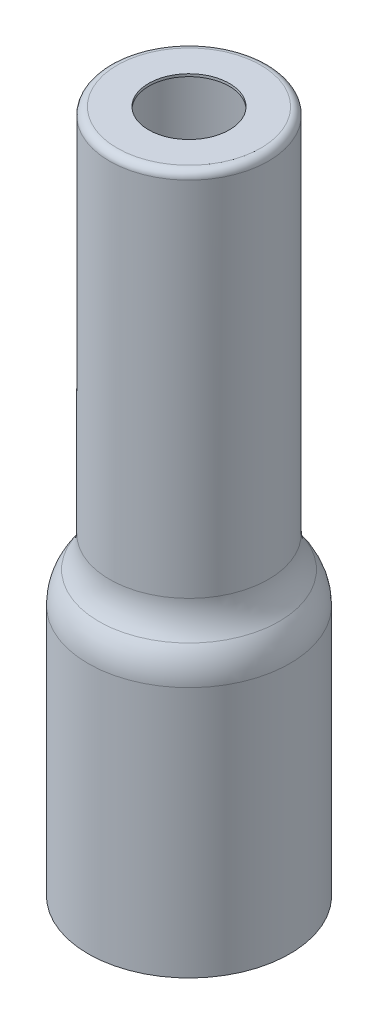
SolidWorks part; units mm, degrees
ref_plane "Спереди" through (0, 0, 0) normal (0, 0, 1) x (1, 0, 0)
ref_plane "Сверху" through (0, 0, 0) normal (0, 1, 0) x (1, 0, 0)
ref_plane "Справа" through (0, 0, 0) normal (1, 0, 0) x (0, 0, -1)
sketch "Эскиз1" plane through (0, 0, 0) normal (0, 1, 0) x (1, 0, 0)
  circle A0 centre (0, 0) radius 40
  circle A1 centre (0, 0) radius 30
extrude "Вытянуть1" add sketch "Эскиз1" along normal blind 43
sketch "Эскиз2" plane through (0, 43, 0) normal (0, 1, 0) x (1, 0, 0)
  circle A0 centre (0, 0) radius 40
extrude "Вытянуть2" add sketch "Эскиз2" along normal blind 65
sketch "Эскиз3" plane through (0, 108, 0) normal (0, 1, 0) x (-1, 0, 0)
  circle A0 centre (0, 0) radius 30.5
  circle A1 centre (0, 0) radius 31.5
extrude "Вытянуть3" add sketch "Эскиз3" along normal blind 162
fillet "Скругление1" radius 20 1 edges at (0, 108, 31.5)
fillet "Скругление2" radius 20 1 edges at (0, 108, 40)
sketch "Эскиз4" plane through (0, 270, 0) normal (0, 1, 0) x (-1, 0, 0)
  circle A0 centre (0, 0) radius 31.5
  circle A1 centre (0, 0) radius 16
extrude "Вытянуть4" add sketch "Эскиз4" along normal blind 1
fillet "Скругление3" radius 3 1 edges at (0, 271, 31.5)
